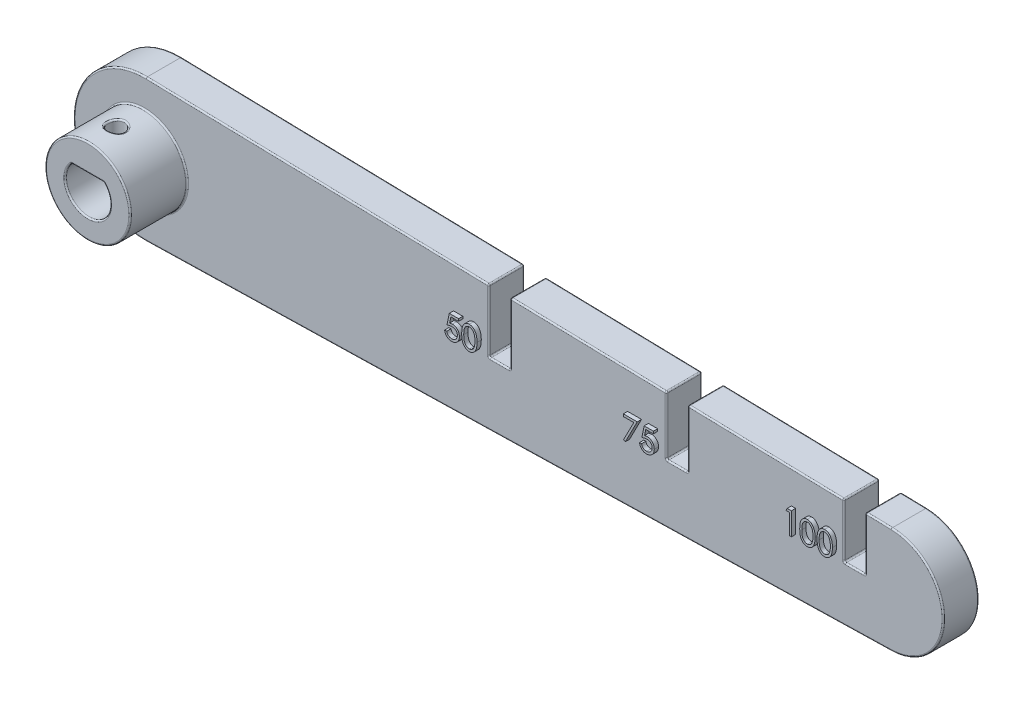
SolidWorks part; units mm, degrees
ref_plane "Front Plane" through (0, 0, 0) normal (0, 0, 1) x (1, 0, 0)
ref_plane "Top Plane" through (0, 0, 0) normal (0, 1, 0) x (1, 0, 0)
ref_plane "Right Plane" through (0, 0, 0) normal (1, 0, 0) x (0, 0, -1)
sketch "Sketch3" plane through (0, 0, 0) normal (0, 0, 1) x (1, 0, 0)
  line L0 (0.2381, 9.9972) -> (105.1786, 7.4979)
  line L1 (105.1786, -7.4979) -> (0.2381, -9.9972)
  arc A0 (0.2381, 9.9972) -> (0.2381, -9.9972) centre (0, 0) ccw
  arc A1 (105.1786, -7.4979) -> (105.1786, 7.4979) centre (105, 0) ccw
  dimension "D1" = 20
  dimension "D2" = 15
  dimension "D3" = 105
extrude "Boss-Extrude1" add sketch "Sketch3" along normal blind 5
sketch "Sketch2" plane through (0, 0, 0) normal (0, 0, 1) x (1, 0, 0)
  line L0 (-2.265, 2.225) -> (2.265, 2.225)
  line L1 (-10.2128, -3.175) -> (10.2128, -3.175) construction
  arc A0 (2.265, 2.225) -> (-2.265, 2.225) centre (0, 0) cw
  point P7 (0, -3.175)
  dimension "D1" = 3.175
  dimension "D2" = 5.4
extrude "Cut-Extrude2" cut sketch "Sketch2" along normal up to next
sketch "Sketch4" plane through (0, 0, 5) normal (0, 0, 1) x (1, 0, 0)
  line L0 (105.1786, 7.4979) -> (0.2381, 9.9972) construction
  line L1 (98.5, 7.6569) -> (101.5, 7.6569)
  line L2 (98.5, 7.6569) -> (98.5, 0)
  line L3 (98.5, 0) -> (101.5, 0)
  line L4 (101.5, 7.6569) -> (101.5, 0)
  line L5 (100, 0) -> (100, 7.6212) construction
  line L6 (0, 0) -> (112.5, 0) construction
  line L7 (73.5, 8.2523) -> (76.5, 8.2523)
  line L8 (73.5, 8.2523) -> (73.5, 0)
  line L9 (73.5, 0) -> (76.5, 0)
  line L10 (76.5, 8.2523) -> (76.5, 0)
  line L11 (75, 0) -> (75, 8.2523) construction
  line L12 (48.5, 8.8477) -> (51.5, 8.8477)
  line L13 (48.5, 8.8477) -> (48.5, 0)
  line L14 (48.5, 0) -> (51.5, 0)
  line L15 (51.5, 8.8477) -> (51.5, 0)
  line L16 (50, 0) -> (50, 8.8477) construction
  arc A0 (105.1786, -7.4979) -> (105.1786, 7.4979) centre (105, 0) ccw construction
  dimension "D3" = 3
  dimension "D4" = 50
  dimension "D5" = 75
  dimension "D6" = 100
extrude "Cut-Extrude3" cut sketch "Sketch4" against normal up to next
sketch "Sketch6" plane through (0, 0, 5) normal (0, 0, 1) x (1, 0, 0)
  line L0 (-2.265, 2.225) -> (2.265, 2.225)
  circle A0 centre (0, 0) radius 6
  arc A1 (2.265, 2.225) -> (-2.265, 2.225) centre (0, 0) cw
  dimension "D1" = 12
extrude "Boss-Extrude3" add sketch "Sketch6" along normal blind 8
sketch "Sketch7" plane through (0, 0, 0) normal (0, 1, 0) x (1, 0, 0)
  line L0 (0, -5) -> (0, -13) construction
  line L1 (-6, -5) -> (6, -5) construction
  line L2 (-6, -13) -> (6, -13) construction
  circle A0 centre (0, -9) radius 1.15
  dimension "D1" = 2.3
extrude "Cut-Extrude4" cut sketch "Sketch7" along normal up to next
fillet "Fillet1" radius 0.2 54 edges at (51.5, 0, 2.5) (48.5, 0, 2.5) (101.5, 0, 2.5) (98.5, 0, 2.5) (76.5, 0, 2.5) (73.5, 0, 2.5) (0, 2.225, 0) (0, -3.175, 0) (76.5, 4.0904, 0) (75, 0, 0) (73.5, 4.1262, 0) (62.5, 8.5143, 0) (51.5, 4.3881, 0) (50, 0, 0) (48.5, 4.4239, 0) (24.369, 9.4225, 0) (-10, 0, 0) (52.7083, -8.7475, 0) (112.5, 0, 0) (103.3393, 7.5417, 0) (101.5, 3.7927, 0) (100, 0, 0) (98.5, 3.8285, 0) (87.5, 7.9189, 0) (100, 0, 5) (101.5, 3.7927, 5) (103.3393, 7.5417, 5) (112.5, 0, 5) (52.7083, -8.7475, 5) (-10, 0, 5) (24.369, 9.4225, 5) (48.5, 4.4239, 5) (50, 0, 5) (51.5, 4.3881, 5) (62.5, 8.5143, 5) (73.5, 4.1262, 5) (75, 0, 5) (76.5, 4.0904, 5) (87.5, 7.9189, 5) (98.5, 3.8285, 5) (101.5, 7.5855, 2.5) (98.5, 7.6569, 2.5) (76.5, 8.1809, 2.5) (73.5, 8.2523, 2.5) (51.5, 8.7763, 2.5) (48.5, 8.8477, 2.5) (6, 0, 5) (0, 2.225, 13) (2.265, 2.225, 6.5) (0, -3.175, 13) (-2.265, 2.225, 6.5) (-0.241, 5.9952, 10.1245) (0, 2.225, 7.85) (6, 0, 13)
sketch "Sketch5" plane through (0, 0, 5) normal (0, 0, 1) x (1, 0, 0)
  line L0 (0, 0) -> (112.3, 0) construction
  line L1 (48.5, 8.6525) -> (48.5, 0.2) construction
  line L2 (73.5, 8.057) -> (73.5, 0.2) construction
  line L3 (98.5, 7.4616) -> (98.5, 0.2) construction
  arc A0 (105.1738, -7.2979) -> (105.1738, 7.2979) centre (105, 0) ccw construction
  text T0 "50"
  text T1 "75"
  text T2 "100"
  dimension "D1" = 5.8
  dimension "D2" = 5.8
  dimension "D3" = 8.2
extrude "Boss-Extrude2" add sketch "Sketch5" along normal blind 0.6
